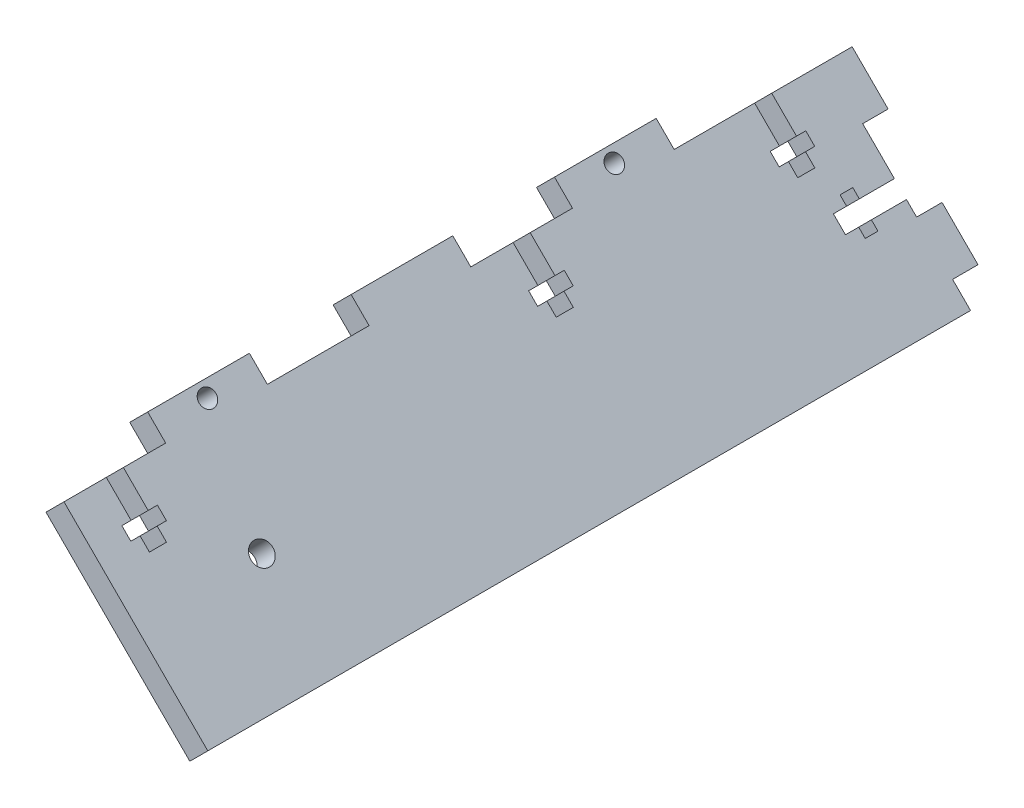
SolidWorks part; units mm, degrees
ref_plane "Front Plane" through (0, 0, 0) normal (0, 0, 1) x (1, 0, 0)
ref_plane "Top Plane" through (0, 0, 0) normal (0, 1, 0) x (1, 0, 0)
ref_plane "Right Plane" through (0, 0, 0) normal (1, 0, 0) x (0, 0, -1)
sketch "Sketch1" plane through (0, 0, 0) normal (0, 0, 1) x (1, 0, 0)
  line L0 (-105.5101, 43.1479) -> (-54.0999, -8.2622) construction
  line L1 (-21.1674, -45.6848) -> (-64.2712, -2.5811) construction
  line L2 (-59.7811, 1.9091) -> (-16.6773, -41.1947) construction
  line L3 (-73.6381, 43.6049) -> (-37.7171, 7.6839)
  line L4 (-73.6381, 43.6049) -> (-69.148, 48.095)
  line L5 (-37.7171, 7.6839) -> (-33.2269, 12.174)
  line L6 (-69.148, 48.095) -> (-33.2269, 12.174)
  line L7 (-70.046, -24.645) -> (-105.967, 11.276) construction
  line L8 (-74.5361, -29.1352) -> (-70.046, -24.645) construction
extrude "Boss-Extrude1" add sketch "Sketch1" along normal up to surface (190.5 mm away)
sketch "Sketch2" plane through (-58.6215, 58.6215, 0) normal (-0.7071, 0.7071, 0) x (0, 0, 1)
  line L0 (190.5, -14.8867) -> (0, -14.8867) construction
  line L1 (165.1, -14.8867) -> (139.7, -14.8867)
  line L2 (165.1, -14.8867) -> (165.1, -21.2367)
  line L3 (165.1, -21.2367) -> (139.7, -21.2367)
  line L4 (139.7, -14.8867) -> (139.7, -21.2367)
  line L5 (190.5, -21.2367) -> (0, -21.2367) construction
  dimension "D1" = 25.4
  dimension "D2" = 25.4
extrude "Boss-Extrude2" add sketch "Sketch2" along normal blind 6.35
pattern_linear "LPattern1" count 3 spacing 50.8 along (0, 0, -1) of "Boss-Extrude2"
sketch "Sketch3" plane through (0, 0, 0) normal (0, 0, -1) x (-1, 0, 0)
  line L0 (73.6381, 43.6049) -> (64.6578, 34.6246)
  line L1 (73.6381, 43.6049) -> (37.7171, 7.6839) construction
  line L2 (64.6578, 34.6246) -> (60.1677, 39.1148)
  line L3 (33.2269, 12.174) -> (69.148, 48.095) construction
  line L4 (60.1677, 39.1148) -> (69.148, 48.095)
  line L5 (69.148, 48.095) -> (73.6381, 43.6049)
  dimension "D1" = 12.7
extrude "Boss-Extrude3" add sketch "Sketch3" along normal blind 6.35
pattern_linear "LPattern2" count 2 spacing 31.75 along (0.7071, -0.7071, 0) of "Boss-Extrude3"
sketch "Sketch4" plane through (-10.5265, -10.5265, 0) normal (0.7071, 0.7071, 0) x (0, 0, -1)
  circle A0 centre (-159.0375, 57.5033) radius 2.7305
extrude "Cut-Extrude1" cut sketch "Sketch4" against normal through all
sketch "Sketch5" plane through (-10.5265, -10.5265, 0) normal (0.7071, 0.7071, 0) x (0, 0, -1)
  line L0 (-177.8, 82.9033) -> (-177.8, 68.4326) construction
  line L1 (-190.5, 82.9033) -> (-165.1, 82.9033) construction
  line L2 (-76.2, 82.9033) -> (-76.2, 62.5112) construction
  line L3 (-88.9, 82.9033) -> (-63.5, 82.9033) construction
  line L4 (-15.875, 82.9033) -> (-15.875, 66.2052) construction
  line L5 (-38.1, 82.9033) -> (6.35, 82.9033) construction
  line L6 (-38.1412, 82.9033) -> (0, 82.9033) construction
  line B0 (-175.6664, 82.9033) -> (-179.9336, 82.9033)
  line B1 (-179.9336, 70.9653) -> (-182.245, 70.9653)
  line B2 (-182.245, 70.9653) -> (-182.245, 74.1403)
  line B3 (-182.245, 74.1403) -> (-179.9336, 74.1403)
  line B4 (-179.9336, 74.1403) -> (-179.9336, 82.9033)
  line B5 (-179.9336, 70.9653) -> (-179.9336, 67.6633)
  line B6 (-179.9336, 67.6633) -> (-175.6664, 67.6633)
  line B7 (-175.6664, 70.9653) -> (-175.6664, 67.6633)
  line B8 (-175.6664, 74.1403) -> (-175.6664, 82.9033)
  line B9 (-173.355, 74.1403) -> (-175.6664, 74.1403)
  line B10 (-173.355, 70.9653) -> (-173.355, 74.1403)
  line B11 (-175.6664, 70.9653) -> (-173.355, 70.9653)
  line B12 (-74.0664, 82.9033) -> (-78.3336, 82.9033)
  line B13 (-78.3336, 70.9653) -> (-80.645, 70.9653)
  line B14 (-80.645, 70.9653) -> (-80.645, 74.1403)
  line B15 (-80.645, 74.1403) -> (-78.3336, 74.1403)
  line B16 (-78.3336, 74.1403) -> (-78.3336, 82.9033)
  line B17 (-78.3336, 70.9653) -> (-78.3336, 67.6633)
  line B18 (-78.3336, 67.6633) -> (-74.0664, 67.6633)
  line B19 (-74.0664, 70.9653) -> (-74.0664, 67.6633)
  line B20 (-74.0664, 74.1403) -> (-74.0664, 82.9033)
  line B21 (-71.755, 74.1403) -> (-74.0664, 74.1403)
  line B22 (-71.755, 70.9653) -> (-71.755, 74.1403)
  line B23 (-74.0664, 70.9653) -> (-71.755, 70.9653)
  line B24 (-13.7414, 82.9033) -> (-18.0086, 82.9033)
  line B25 (-18.0086, 70.9653) -> (-20.32, 70.9653)
  line B26 (-20.32, 70.9653) -> (-20.32, 74.1403)
  line B27 (-20.32, 74.1403) -> (-18.0086, 74.1403)
  line B28 (-18.0086, 74.1403) -> (-18.0086, 82.9033)
  line B29 (-18.0086, 70.9653) -> (-18.0086, 67.6633)
  line B30 (-18.0086, 67.6633) -> (-13.7414, 67.6633)
  line B31 (-13.7414, 70.9653) -> (-13.7414, 67.6633)
  line B32 (-13.7414, 74.1403) -> (-13.7414, 82.9033)
  line B33 (-11.43, 74.1403) -> (-13.7414, 74.1403)
  line B34 (-11.43, 70.9653) -> (-11.43, 74.1403)
  line B35 (-13.7414, 70.9653) -> (-11.43, 70.9653)
sketch_block_instance "TSlot-1"
sketch_block "TSlot" parameters "D1"=3.302, "D2"=3.175
sketch_block_instance "TSlot-2"
sketch_block_instance "TSlot-3"
extrude "Cut-Extrude2" cut sketch "Sketch5" against normal through all
sketch "Sketch6" plane through (-15.0166, -15.0166, 0) normal (-0.7071, -0.7071, 0) x (0, 0, 1)
  line L0 (150.287, 89.2533) -> (154.5542, 82.9033) construction
  line L1 (139.7, 89.2533) -> (165.1, 89.2533) construction
  line L2 (150.287, 89.2533) -> (150.287, 82.9033) construction
  line L3 (154.5542, 89.2533) -> (150.287, 82.9033) construction
  line L4 (154.5542, 82.9033) -> (154.5542, 89.2533) construction
  line L5 (48.687, 89.2533) -> (52.9542, 82.9033) construction
  line L6 (38.1, 89.2533) -> (63.5, 89.2533) construction
  line L7 (48.687, 89.2533) -> (48.687, 82.9033) construction
  line L8 (52.9542, 89.2533) -> (48.687, 82.9033) construction
  line L9 (52.9542, 82.9033) -> (52.9542, 89.2533) construction
  circle A0 centre (152.4206, 86.0783) radius 2.0955
  circle A1 centre (50.8206, 86.0783) radius 2.0955
  dimension "D1" = 4.191
extrude "Cut-Extrude3" cut sketch "Sketch6" against normal through all
sketch "Sketch7" plane through (-10.5265, -10.5265, 0) normal (0.7071, 0.7071, 0) x (0.7071, -0.7071, 0)
  line L0 (-56.8683, 0) -> (-56.8683, -24.4742) construction
  line L1 (-51.1533, 0) -> (-70.2033, 0) construction
  line L4 (-67.6633, -18.0086) -> (-67.6633, -13.7414) construction
  line B0 (-54.7347, 0) -> (-59.0019, 0)
  line B1 (-59.0019, -11.938) -> (-61.3133, -11.938)
  line B2 (-61.3133, -11.938) -> (-61.3133, -8.763)
  line B3 (-61.3133, -8.763) -> (-59.0019, -8.763)
  line B4 (-59.0019, -8.763) -> (-59.0019, 0)
  line B5 (-59.0019, -11.938) -> (-59.0019, -15.24)
  line B6 (-59.0019, -15.24) -> (-54.7347, -15.24)
  line B7 (-54.7347, -11.938) -> (-54.7347, -15.24)
  line B8 (-54.7347, -8.763) -> (-54.7347, 0)
  line B9 (-52.4233, -8.763) -> (-54.7347, -8.763)
  line B10 (-52.4233, -11.938) -> (-52.4233, -8.763)
  line B11 (-54.7347, -11.938) -> (-52.4233, -11.938)
  dimension "D1" = 6.35
sketch_block_instance "TSlot-4"
extrude "Cut-Extrude4" cut sketch "Sketch7" against normal through all
